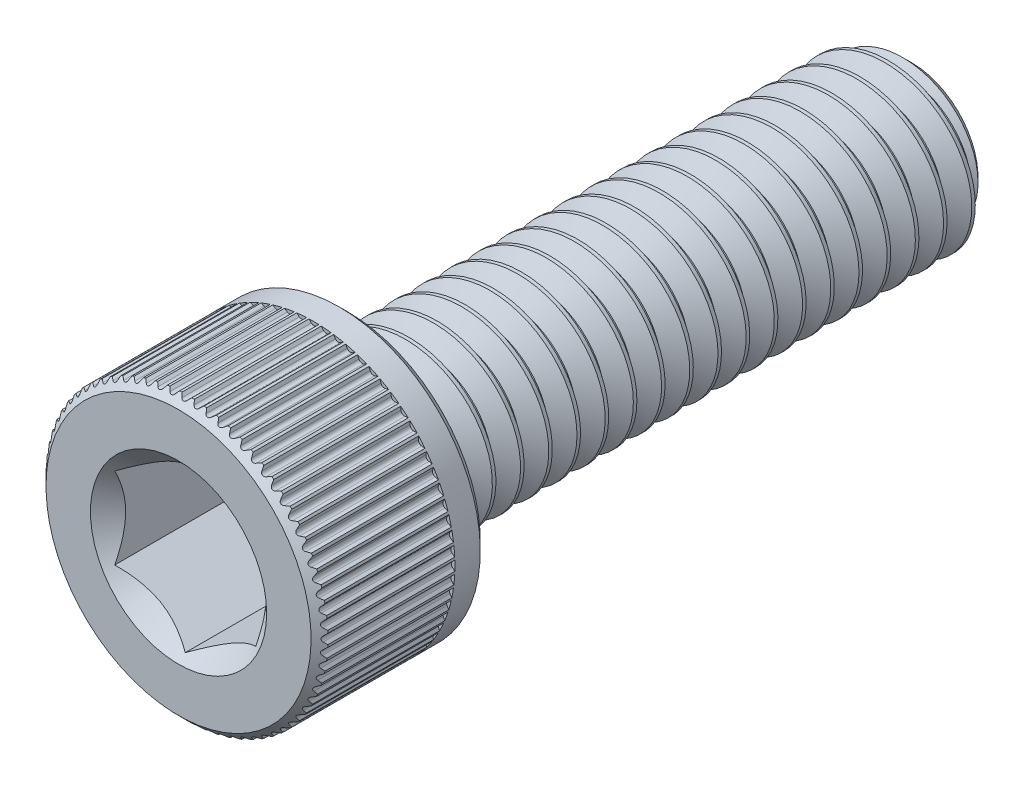
SolidWorks part; units mm, degrees
ref_plane "Front Plane" through (0, 0, 0) normal (0, 0, 1) x (1, 0, 0)
ref_plane "Top Plane" through (0, 0, 0) normal (0, 1, 0) x (1, 0, 0)
ref_plane "Right Plane" through (0, 0, 0) normal (1, 0, 0) x (0, 0, -1)
sketch "Sketch1" plane through (0, 0, 0) normal (1, 0, 0) x (0, 0, -1)
  line L0 (-13, 0) -> (13, 0) construction
  line L1 (13, 0) -> (13, 2.3505) construction
  line L2 (13, 2.3505) -> (12.3505, 3) construction
  line L3 (12.3505, 3) -> (12.25, 3) construction
  line L4 (12.25, 3) -> (-7, 3) construction
  line L5 (-7, 3) -> (-7, 5) construction
  line L6 (-7, 5) -> (-13, 5) construction
  line L7 (-13, 5) -> (-13, 0) construction
  line L8 (13, 2.3505) -> (13, 3) construction
  line L9 (12.9375, 3.1083) -> (13.4375, 2.2422) construction
  line L10 (13.4375, 2.2422) -> (13.9375, 3.1083) construction
  line L11 (13.9375, 3.1083) -> (12.9375, 3.1083) construction
  line L12 (13.4375, 3.1083) -> (13.4375, 3) construction
  line L13 (13.4375, 2.2422) -> (13.4375, 2.3505) construction
  line L14 (13.375, 2.3505) -> (13.5, 2.3505) construction
  line L15 (13, 3) -> (13.875, 3) construction
  line L16 (12.9688, 3.0541) -> (13.9062, 3.0541) construction
  line L17 (13, 0) -> (13, -3) construction
  line L18 (-7.3, 5) -> (-7, 4.7) construction
  line L19 (-12.7, 5) -> (-13, 4.7) construction
  line L20 (-7, 3) -> (-7, 0) construction
  line L21 (-7, 1.5) -> (-0.3333, 1.5) construction
  line L22 (-0.3333, 1.5) -> (6.3333, 1.5) construction
  line L23 (6.3333, 1.5) -> (13, 1.5) construction
  line L24 (-0.3333, 1.5) -> (-0.3333, 3) construction
  line L25 (-0.3333, 3) -> (-0.3333, 5) construction
  line L26 (6.3333, 1.5) -> (6.3333, 5) construction
  point P0 (-13, 2.5)
  point P3 (10.5, 3)
  point P4 (0, 0)
  point P18 (6.3333, 3)
  point P22 (13.4375, 2.3505)
  point P24 (12.25, 3)
  point P25 (13.4375, 3)
  point P28 (13.4375, 3.0541)
  point P29 (10.5, -3)
  point P30 (-0.3333, 3)
  point P31 (-10, 5)
  point P37 (-8.05, 5)
  point P38 (-12.55, 5)
  point P45 (-0.3333, 1.5)
  point P46 (6.3333, 1.5)
  dimension "D2" = 0.125
  dimension "D7" = 0.3
  dimension "D8" = 0.3
  dimension "D9" = 0.3
  dimension "D10" = 0.15
  dimension "D11" = 0.75
  dimension "Drive Size" = 5
  dimension "Head Diameter" = 10
  dimension "Head Height" = 6
  dimension "Thread Pitch" = 1
  dimension "Thread Size" = 6
  dimension "Length" = 20
  dimension "D12" = 0.75
  dimension "D4" = 2.5
  dimension "D3" = 45
sketch "Sketch2" plane through (0, 0, 0) normal (1, 0, 0) x (0, 0, -1)
  line L0 (-13, 0) -> (-13, 4.7)
  line L1 (-12.7, 5) -> (-7.3, 5)
  line L2 (-7, 4.7) -> (-7, 3.3)
  line L4 (12.3505, 3) -> (13, 2.3505)
  line L5 (13, 2.3505) -> (13, 0)
  line L6 (-7, 5) -> (-13, 5) construction
  line L7 (13, 0) -> (-13, 0)
  line L8 (-12.7, 5) -> (-13, 4.7) construction
  line L10 (-12.7, 5) -> (-13, 4.7)
  line L14 (-7.3, 5) -> (-7, 4.7) construction
  line L16 (-7.3, 5) -> (-7, 4.7)
  line L17 (-7, 3) -> (-7, 5) construction
  line L19 (-6.7, 3) -> (12.3505, 3)
  line L20 (12.25, 3) -> (-7, 3) construction
  arc A1 (-7, 3.3) -> (-6.7, 3) centre (-6.7, 3.3) ccw
  dimension "D3" = 0.3
revolve "Revolve1" add sketch "Sketch2" angle 360 about L7
sketch "Sketch3" plane through (0, 0, 13) normal (0, 0, 1) x (1, 0, 0)
  line L1 (2.5, -1.4434) -> (2.5, 1.4434)
  line L2 (2.5, 1.4434) -> (0, 2.8868)
  line L3 (0, 2.8868) -> (-2.5, 1.4434)
  line L4 (-2.5, 1.4434) -> (-2.5, -1.4434)
  line L5 (-2.5, -1.4434) -> (0, -2.8868)
  line L6 (0, -2.8868) -> (2.5, -1.4434)
  circle A0 centre (0, 0) radius 2.5 construction
  circle A1 centre (0, 0) radius 5 construction
  circle A2 centre (0, 0) radius 5 construction
  circle A3 centre (0, 0) radius 2.8868 construction
  point P13 (0, 0)
extrude "Cut-Extrude1" cut sketch "Sketch3" against normal offset from surface (5 mm away) 1 up to face at (0, 4.7, 7)
sketch "Sketch4" plane through (0, 0, 13) normal (0, 0, 1) x (1, 0, 0)
  circle A0 centre (0, 0) radius 3.125
  dimension "D1" = 6.25
extrude "Cut-Extrude2" cut sketch "Sketch4" against normal up to vertex (3 mm away) draft 45 up to point (0, 5, 10)
sketch "Sketch11" plane through (0, 0, 0) normal (1, 0, 0) x (0, 0, -1)
  line L0 (-13, 0) -> (13, 0) construction
  line L1 (-13, 0) -> (13, 0) construction
  line L2 (-3.25, 0) -> (-3.25, 3) construction
  line L3 (12.25, 3) -> (-7, 3) construction
  line L4 (9.25, 0) -> (9.25, 3) construction
  line L6 (13, 2.3505) -> (13, 3) construction
  point P2 (-3.25, 0)
  point P3 (9.25, 0)
  dimension "D1" = 3.75
  dimension "D2" = 3.75
sketch "Sketch6" plane through (0, 0, -13) normal (0, 0, -1) x (-1, 0, 0)
  circle A0 centre (0, 0) radius 3
curve "Helix/Spiral1" pitch 1 height 21 radius 3 centre (0, 0, -13) axis (0, 0, 1) start towards (0, 1, 0)
sketch "Sketch10" plane through (0, 0, 0) normal (1, 0, 0) x (0, 0, -1)
  line L0 (-6.7, -5) -> (-6.7, 5)
  line L5 (-13, 0) -> (13, 0) construction
  line L6 (-6.7, 3) -> (-6.7, -3) construction
  point P3 (-6.7, 0)
split "Split1" trim tools "Sketch10" bodies to split 106 resulting bodies 114 115
sketch "Sketch7" plane through (0, 0, 0) normal (1, 0, 0) x (0, 0, -1)
  line L0 (12.9688, 3.0541) -> (13.9062, 3.0541)
  line L1 (13.9062, 3.0541) -> (13.5, 2.3505)
  line L2 (13.5, 2.3505) -> (13.375, 2.3505)
  line L3 (13.375, 2.3505) -> (12.9688, 3.0541)
sweep "Cut-Sweep1" cut profiles "Sketch7" path "Helix/Spiral1" align with end faces yes
sketch "Sketch8" plane through (0, 0, 0) normal (1, 0, 0) x (0, 0, -1)
  line L0 (-7, 0) -> (-7, 3)
  line L1 (-6.7, -3) -> (-6.7, 3) construction
  line L2 (-7, 3) -> (-6.7, 3)
  line L4 (-6.7, 3) -> (-4.9679, 0)
  line L5 (-4.9679, 0) -> (-7, 0)
  line L6 (12.25, 3) -> (-7, 3) construction
  line L7 (-13, 0) -> (13, 0) construction
  dimension "D1" = 60
revolve "Revolve2" add sketch "Sketch8" angle 360 about L5
ref_plane "Plane1" through (0, 0, 13) normal (0, 0, 1) x (1, 0, 0)
sketch "Sketch12" plane through (0, 0, 13) normal (0, 0, 1) x (1, 0, 0)
  line L0 (0, 0) -> (0.1745, 4.997) construction
  line L1 (0, 0) -> (-0.1745, 4.997) construction
  line L2 (0, 4.875) -> (0, 5.125) construction
  line L3 (-0.3025, 5.125) -> (0.3025, 5.125)
  line L4 (-0.3025, 5.125) -> (-0.0897, 4.9122)
  line L5 (0.0897, 4.9122) -> (0.3025, 5.125)
  circle A0 centre (0, 0) radius 5 construction
  arc A1 (-0.0897, 4.9122) -> (0.0897, 4.9122) centre (0, 5.0019) ccw
  point P9 (0, 5.125)
  point P13 (0, 5)
  dimension "D2" = 0.125
extrude "Cut-Extrude3" cut sketch "Sketch12" against normal blind 4.8
pattern_circular "CirPattern1" count 72 over 360 about axis through (0, 0, 13) along (0, 0, -1) of "Cut-Extrude3"
equation "\"D2@Sketch1\" = \"Thread Pitch@Sketch1\" / 8"
equation "\"D4@Helix/Spiral1\" = \"Thread Pitch@Sketch1\""
equation "\"D7@Sketch1\" = \"Head Height@Sketch1\" * .05"
equation "\"D8@Sketch1\"=\"D7@Sketch1\""
equation "\"D9@Sketch1\"=\"D7@Sketch1\""
equation "\"D10@Sketch1\"=\"D7@Sketch1\"/2"
equation "\"D11@Sketch1\"=\"D10@Sketch1\"*5"
equation "\"D4@Sketch1\"=\"Thread Pitch@Sketch1\"*2.5"
equation "\"D12@Sketch1\"=\"Thread Pitch@Sketch1\"*.75"
equation "\"D3@Helix/Spiral1\"=\"Length@Sketch1\"+\"Thread Pitch@Sketch1\""
equation "\"D3@Sketch2\" = \"Thread Size@Sketch1\" * 0.05"
equation "\"D1@Sketch11\"=\"Length@Sketch1\"*0.1875"
equation "\"D2@Sketch11\"=\"D1@Sketch11\""
equation "\"D2@Sketch12\"=\"Head Diameter@Sketch1\"*.0125"
equation "\"D1@Cut-Extrude3\"=\"Head Height@Sketch1\"*.8"
equation "\"D1@CirPattern1\"=\"D3@CirPattern1\"/(1.25*\"D1@Sketch12\")"
equation "\"D1@Sketch4\"=\"Drive Size@Sketch1\"*1.25"
